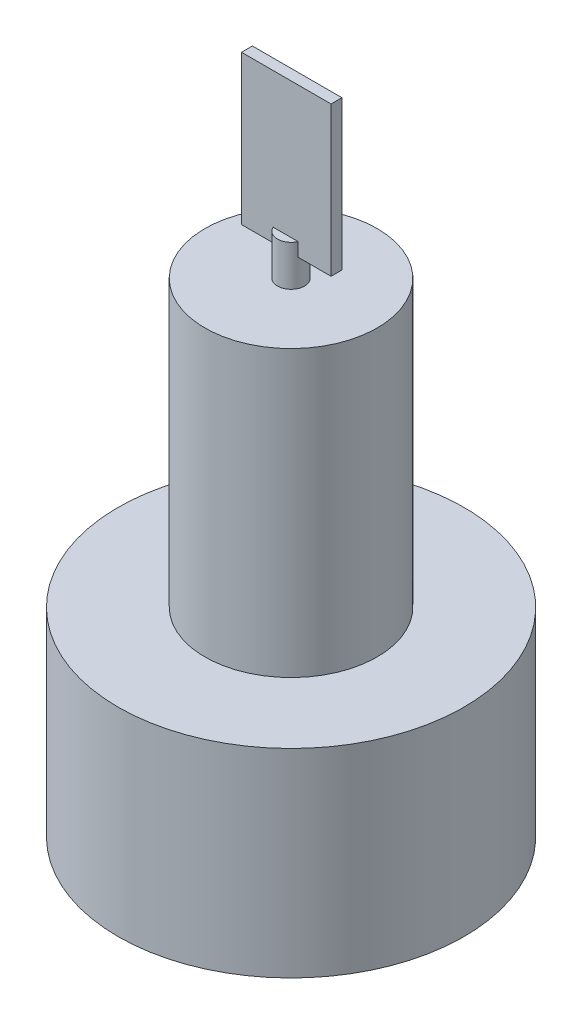
SolidWorks part; units mm, degrees
ref_plane "前视基准面" through (0, 0, 0) normal (0, 0, 1) x (1, 0, 0)
ref_plane "上视基准面" through (0, 0, 0) normal (0, 1, 0) x (1, 0, 0)
ref_plane "右视基准面" through (0, 0, 0) normal (1, 0, 0) x (0, 0, -1)
sketch "草图1" plane through (0, 0, 0) normal (0, 1, 0) x (1, 0, 0)
  circle A0 centre (0, 0) radius 12.75
  dimension "D1" = 25.5
extrude "凸台-拉伸1" add sketch "草图1" along normal blind 14.65
sketch "草图2" plane through (0, 14.65, 0) normal (0, 1, 0) x (1, 0, 0)
  circle A0 centre (0, 0) radius 6.35
  dimension "D1" = 12.7
extrude "凸台-拉伸2" add sketch "草图2" along normal blind 21
sketch "草图3" plane through (0, 35.65, 0) normal (0, 1, 0) x (1, 0, 0)
  circle A0 centre (0, 0) radius 1
  dimension "D1" = 2
extrude "凸台-拉伸3" add sketch "草图3" along normal blind 3
sketch "草图4" plane through (0, 0, 0) normal (0, 0, 1) x (1, 0, 0)
  line L0 (-3.25, 37.65) -> (3.35, 37.65)
  line L5 (3.35, 37.65) -> (3.35, 48.65)
  line L6 (3.35, 48.65) -> (-3.25, 48.65)
  line L7 (-3.25, 48.65) -> (-3.25, 37.65)
  line L8 (6.35, 35.65) -> (-6.35, 35.65) construction
  line L9 (6.35, 35.65) -> (-6.35, 35.65)
  line L10 (6.35, 14.65) -> (6.35, 35.65) construction
  dimension "D1" = 6.6
  dimension "D2" = 11
  dimension "D3" = 2
  dimension "D4" = 3
extrude "凸台-拉伸4" add sketch "草图4" along normal blind 0.4 and the other way blind 0.4 contours L6 L7 L0 L5 region at (0.05, 43.15, 0)
